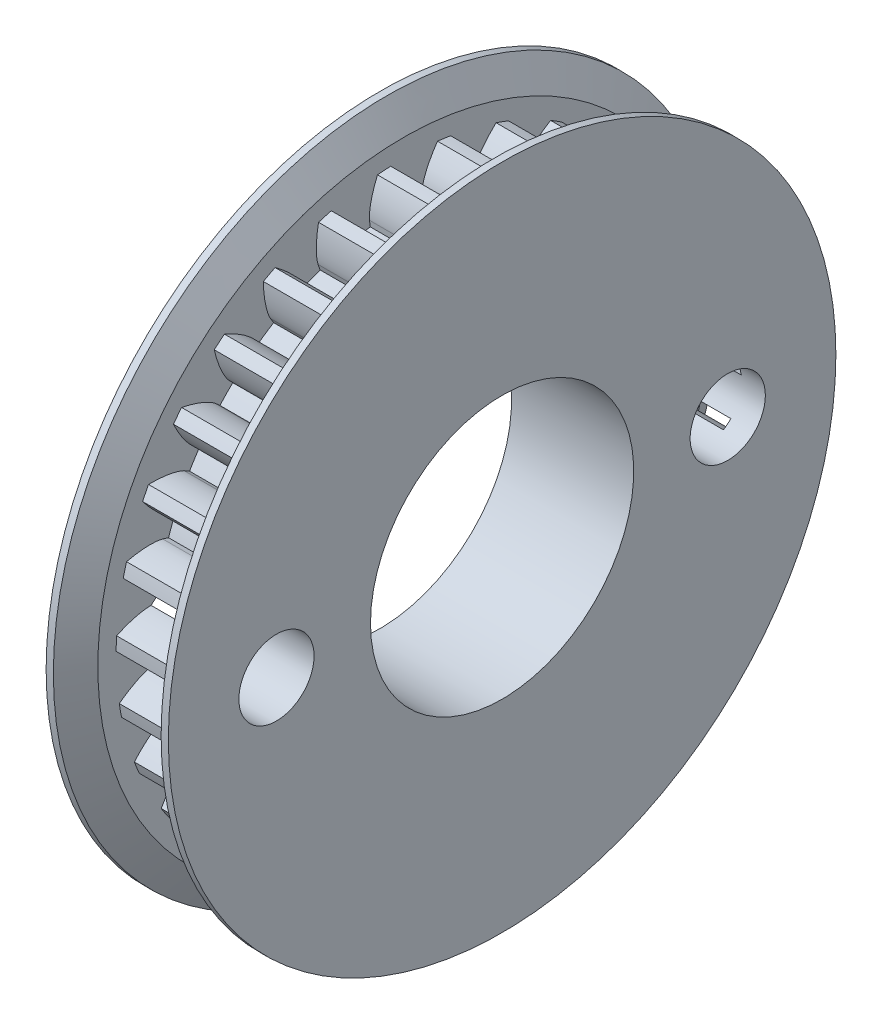
SolidWorks part; units mm, degrees
material "6061-T6 (SS)"
ref_plane "Front Plane" through (0, 0, 0) normal (1, 0, 0) x (0, 1, 0)
ref_plane "Top Plane" through (0, 0, 0) normal (0, 0, 1) x (0, 1, 0)
ref_plane "Right Plane" through (0, 0, 0) normal (0, 1, 0) x (-1, 0, 0)
sketch "Sketch1" plane through (0, 0, 0) normal (1, 0, 0) x (0, 1, 0)
  circle A0 centre (0, 0) radius 15.2789
  circle A1 centre (0, 0) radius 13.4601 construction
  circle A2 centre (0, 0) radius 13.1303 construction
  circle A3 centre (0, 0) radius 14.3239 construction
  dimension "D1" = 30.5577
  dimension "D2" = 26.9202
  dimension "D3" = 26.2606
  dimension "D4" = 28.6479
extrude "Boss-Extrude1" add sketch "Sketch1" along normal blind 4
sketch "Sketch3" plane through (4, 0, 0) normal (1, 0, 0) x (0, 1, 0)
  line L0 (0, 0) -> (13.4601, 0) construction
  line L1 (0, 0) -> (14.3224, 0.2135) construction
  line L2 (0, 0) -> (14.3139, -0.5364) construction
  line L3 (14.3139, -0.5364) -> (13.4507, -0.504)
  line L4 (14.3139, -0.5364) -> (18.5988, -0.697)
  line L5 (18.5988, 4.0538) -> (18.5988, -0.697)
  line L6 (13.4601, 0) -> (13.1303, 0)
  line L7 (13.4507, -0.504) -> (13.1211, -0.4917)
  circle A0 centre (0, 0) radius 14.3239 construction
  circle A1 centre (0, 0) radius 13.4601 construction
  circle A2 centre (0, 0) radius 13.1303 construction
  arc A3 (13.1303, 0) -> (13.1211, -0.4917) centre (0, 0) cw
  spline S0 degree 4 poles (13.4601, 0) (13.4701, 0.0002) (13.4979, 0.0015) (13.5506, 0.0064) (13.636, 0.018) (13.7443, 0.0382) (13.8832, 0.0704) (14.0453, 0.1161) (14.2215, 0.1744) (14.4107, 0.2463) (14.5971, 0.3257) (14.7807, 0.4117) (14.9611, 0.5036) (15.1768, 0.6221) (15.431, 0.7741) (15.7213, 0.9659) (16.0419, 1.1999) (16.3586, 1.4553) (16.6618, 1.7205) (16.9576, 2.0036) (17.2363, 2.2883) (17.5142, 2.5988) (17.7648, 2.893) (18.0319, 3.2381) (18.2435, 3.5212) (18.5074, 3.9105) (18.6587, 4.145) (18.8304, 4.4247) (18.9037, 4.5516) (18.9489, 4.6297) knots 0 0 0 0 0 0.005377 0.015084 0.028532 0.04661 0.064855 0.092111 0.119476 0.146842 0.174209 0.201575 0.228941 0.256307 0.307035 0.361767 0.4165 0.471232 0.525964 0.580697 0.635429 0.690161 0.744894 0.799626 0.854358 0.909091 0.954545 1 1 1 1 1 construction
  spline S1 degree 4 poles (13.4601, 0) (13.4701, 0.0002) (13.4979, 0.0015) (13.5506, 0.0064) (13.636, 0.018) (13.7443, 0.0382) (13.8832, 0.0704) (14.0453, 0.1161) (14.2215, 0.1744) (14.4107, 0.2463) (14.5971, 0.3257) (14.7807, 0.4117) (14.9611, 0.5036) (15.1768, 0.6221) (15.431, 0.7741) (15.7213, 0.9659) (16.0419, 1.1999) (16.3586, 1.4553) (16.6618, 1.7205) (16.9576, 2.0036) (17.2363, 2.2883) (17.5142, 2.5988) (17.7648, 2.893) (18.0319, 3.2381) (18.2435, 3.5212) (18.4502, 3.8261) (18.5491, 3.9763) (18.5988, 4.0538) knots 0 0 0 0 0 0.005377 0.015084 0.028532 0.04661 0.064855 0.092111 0.119476 0.146842 0.174209 0.201575 0.228941 0.256307 0.307035 0.361767 0.4165 0.471232 0.525964 0.580697 0.635429 0.690161 0.744894 0.799626 0.854358 0.909091 0.909091 0.909091 0.909091 0.909091
  circle M1 centre (0, 0) radius 15.2789
extrude "Cut-Extrude1" cut sketch "Sketch3" against normal through all contours S1 L6 A3 L3 L4 M1 region at (4, 14.3868, -0.1252)
mirror "Mirror1" about plane through (0, 0, 0) normal (0, 0.0374, 0.9993) of "Cut-Extrude1"
pattern_circular "CirPattern6" count 30 over 360 about axis through (4, 0, 0) along (-1, 0, 0) of "Cut-Extrude1", "Mirror1"
sketch "Sketch5" plane through (0, 0, 0) normal (0, 1, 0) x (-1, 0, 0)
  line L0 (-15.044, 0) -> (9.7198, 0) construction
  line L1 (-4, 0) -> (-5.25, 0)
  line L2 (-5.25, 0) -> (-5.25, 17.7509)
  line L4 (-4, 16.2509) -> (-4, 0)
  line L5 (0, 0) -> (1.25, 0)
  line L6 (0, 13.1303) -> (0, -13.1303) construction
  line L7 (1.25, 0) -> (1.25, 17.7509)
  line L9 (0, 16.2509) -> (0, 0)
  line L10 (-5.25, 17.7509) -> (-4.866, 17.7509)
  line L11 (-4.866, 17.7509) -> (-4, 16.2509)
  line L12 (0, 16.2509) -> (0.866, 17.7509)
  line L13 (0.866, 17.7509) -> (1.25, 17.7509)
  line L15 (0, 15.2509) -> (-4, 15.2509) construction
  point P16 (-4, 16.1793)
  dimension "D1" = 150
  dimension "D2" = 150
  dimension "D3" = 1
  dimension "D4" = 1.5
  dimension "D5" = 1.25
  dimension "D6" = 1.25
revolve "Revolve1" add sketch "Sketch5" angle 360 about L0
sketch "Sketch6" plane through (-1.25, 0, 0) normal (-1, 0, 0) x (0, -1, 0)
  circle A0 centre (0, 0) radius 7
  dimension "D1" = 14
extrude "Cut-Extrude2" cut sketch "Sketch6" against normal through all
sketch "Sketch7" plane through (0, 0, 0) normal (1, 0, 0) x (0, 1, 0)
  line L0 (0, -12) -> (0, 12) construction
  circle A0 centre (0, 12) radius 2
  circle A1 centre (0, -12) radius 2
  point P5 (0, 0)
  dimension "D1" = 4
  dimension "D2" = 24
extrude "Cut-Extrude3" cut sketch "Sketch7" against normal through all both and the other way through all
equation "\"DiametralPitch\"= pi / \"Pitch\""
equation "\"NumberTeeth\"= 30"
equation "\"PressureAngle\"= 20"
equation "\"PitchDiameter\"= \"NumberTeeth\" / \"DiametralPitch\""
equation "\"BaseDiameter\"= \"PitchDiameter\" * cos ( \"PressureAngle\" )"
equation "\"Addendum\"= 1 / \"DiametralPitch\""
equation "\"Dedendum\"= 1.25 / \"DiametralPitch\""
equation "\"AddendumDiameter\"= \"PitchDiameter\" + \"Addendum\" + \"Addendum\""
equation "\"DedendumDiameter\"= \"PitchDiameter\" - \"Dedendum\" - \"Dedendum\""
equation "\"ToothSpacing\"= 360 / ( 4 * \"NumberTeeth\" )"
equation "\"D1@Sketch1\"=\"AddendumDiameter\""
equation "\"D2@Sketch1\"=\"BaseDiameter\""
equation "\"D3@Sketch1\"=\"DedendumDiameter\""
equation "\"D4@Sketch1\"=\"PitchDiameter\""
equation "\"D1@Sketch3\"=\"ToothSpacing\""
equation "\"D1@CirPattern6\"=\"NumberTeeth\""
equation "\"Pitch\"= 3"
